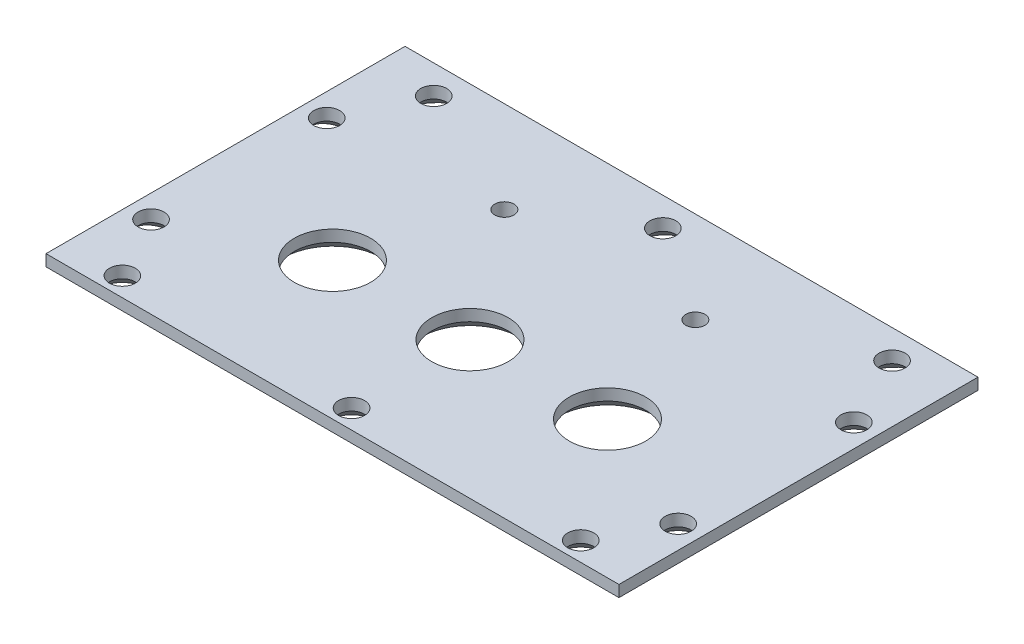
SolidWorks part; units mm, degrees
material "POM Ацеталь кополимер"
ref_plane "Спереди" through (0, 0, 0) normal (0, 0, 1) x (1, 0, 0)
ref_plane "Сверху" through (0, 0, 0) normal (0, 1, 0) x (1, 0, 0)
ref_plane "Справа" through (0, 0, 0) normal (1, 0, 0) x (0, 0, -1)
sketch "Эскиз1" plane through (0, 0, 0) normal (0, 1, 0) x (1, 0, 0)
  line L0 (-18, -29) -> (0, -29) construction
  line L1 (-37.5, 0) -> (37.5, 0)
  line L2 (-37.5, 0) -> (-37.5, -47)
  line L3 (-37.5, -47) -> (37.5, -47)
  line L4 (37.5, 0) -> (37.5, -47)
  line L7 (0, -29) -> (18, -29) construction
  circle A3 centre (18, -29) radius 5
  circle A6 centre (-18, -29) radius 5
  circle A7 centre (0, -29) radius 5
  point P13 (0, 0)
  dimension "D3" = 10
  dimension "D6" = 10
  dimension "D4" = 36
  dimension "D1" = 75
  dimension "D2" = 47
  dimension "D5" = 29
extrude "База" add sketch "Эскиз1" along normal blind 3
hole_wizard "Крепление-M3" positions "Эскиз4" profile "Эскиз3" countersink size "M3" standard "ISO" end condition through all
sketch "Эскиз4" plane through (0, 0, 0) normal (0, -1, 0) x (-1, 0, 0)
  line L0 (0, -44.5) -> (0, -47) construction
  line L1 (37.5, -47) -> (-37.5, -47) construction
  line L8 (30, -44.5) -> (0, -44.5) construction
  line L9 (0, -44.5) -> (-30, -44.5) construction
  line L10 (34.5, -36.25) -> (34.5, -24.75) construction
  line L11 (34.5, -24.75) -> (34.5, -13.25) construction
  line L18 (34.5, -13.25) -> (37.5, -13.25) construction
  line L19 (37.5, 0) -> (37.5, -47) construction
  line L22 (-34.5, -13.25) -> (-37.5, -13.25) construction
  line L23 (-37.5, -47) -> (-37.5, 0) construction
  line L24 (-37.5, 0) -> (37.5, 0) construction
  point P0 (0, -44.5)
  point P2 (-30, -44.5)
  point P4 (30, -44.5)
  point P6 (0, -3.75)
  point P8 (30, -3.75)
  point P10 (-30, -3.75)
  point P34 (34.5, -36.25)
  point P36 (-34.5, -36.25)
  point P38 (-34.5, -13.25)
  point P40 (34.5, -13.25)
  dimension "D1" = 2.5
  dimension "D2" = 60
  dimension "D3" = 23
  dimension "D4" = 3
  dimension "D5" = 3.75
  dimension "D6" = 24.75
sketch "Эскиз3" plane through (0, 0, 44.5) normal (1, 0, 0) x (0, 0, -1)
  line L0 (0, 0) -> (0, 3)
  line L1 (0, 3) -> (1.7, 3)
  line L2 (1.7, 3) -> (1.7, 1.45)
  line L3 (1.7, 1.45) -> (3.15, 0)
  line L5 (3.15, 0) -> (0, 0)
  line L6 (-1.7, 1.45) -> (-3.15, 0) construction
  line L11 (0, -6.35) -> (0, 107.95) construction
  dimension "Диаметр сквозного отверстия" = 3.4
  dimension "Глубина сквозного отверстия" = 3
  dimension "Диаметр передней зенковки" = 6.3
  dimension "Угол передней зенковки" = 90
hole_wizard "Укладчик-M3" positions "Эскиз5" profile "Эскиз6" tap size "M3" standard "DIN" end condition through all
sketch "Эскиз5" plane through (0, 0, 0) normal (0, -1, 0) x (-1, 0, 0)
  line L0 (12.5, -12) -> (0, -12) construction
  line L1 (0, -12) -> (-12.5, -12) construction
  point P0 (12.5, -12)
  point P2 (-12.5, -12)
  dimension "D1" = 12
  dimension "D2" = 25
sketch "Эскиз6" plane through (-12.5, 0, 12) normal (1, 0, 0) x (0, 0, -1)
  line L0 (0, 0) -> (0, 3)
  line L1 (0, 3) -> (1.25, 3)
  line L2 (1.25, 3) -> (1.25, 0)
  line L5 (1.25, 0) -> (0, 0)
  line L11 (0, -6.35) -> (0, 107.95) construction
  dimension "Диаметр проходного сверла" = 2.5
  dimension "Глубина проходного сверла" = 3
cosmetic thread "Отверстие резьбы1" parameters "D2"=3
cosmetic thread "Отверстие резьбы2" parameters "D2"=3
chamfer "Фаска1" distance 1.5 angle 45 14 edges at (-37.5, 0, 42.1052) (-37.5, 0, 6.1448) (37.5, 0, 42.1052) (37.5, 0, 6.1448) (34.7082, 0, 47) (-34.7082, 0, 47) (37.5, 0, 24.75) (-37.5, 0, 24.75) (0, 0, 0) (15, 0, 47) (-15, 0, 47) (18, 0, 34) (0, 0, 34) (-18, 0, 34)
